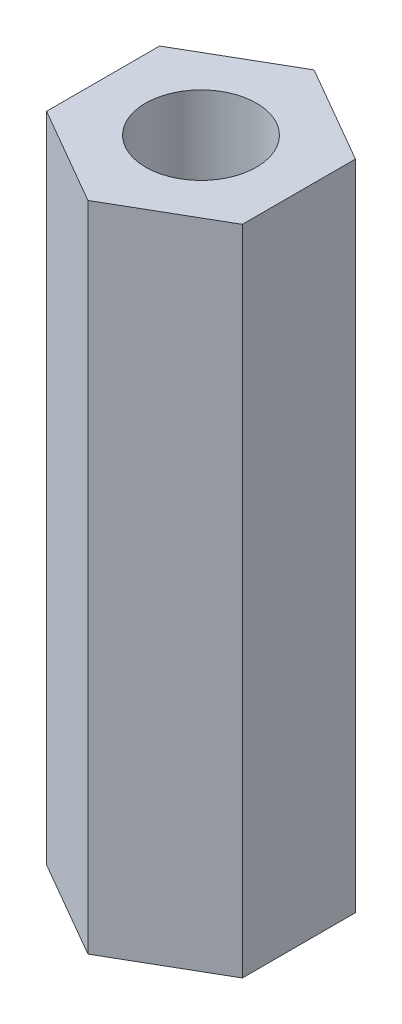
SolidWorks part; units mm, degrees
ref_plane "Front Plane" through (0, 0, 0) normal (0, 0, 1) x (1, 0, 0)
ref_plane "Top Plane" through (0, 0, 0) normal (0, 1, 0) x (1, 0, 0)
ref_plane "Right Plane" through (0, 0, 0) normal (1, 0, 0) x (0, 0, -1)
sketch "Sketch1" plane through (0, 0, 0) normal (0, 1, 0) x (1, 0, 0)
  line L1 (0, -1.7321) -> (1.5, -0.866)
  line L2 (1.5, -0.866) -> (1.5, 0.866)
  line L3 (1.5, 0.866) -> (0, 1.7321)
  line L4 (0, 1.7321) -> (-1.5, 0.866)
  line L5 (-1.5, 0.866) -> (-1.5, -0.866)
  line L6 (-1.5, -0.866) -> (0, -1.7321)
  circle A0 centre (0, 0) radius 1.5 construction
  circle A1 centre (0, 0) radius 0.85
  dimension "D2" = 1.7
  dimension "D1" = 3
extrude "Boss-Extrude1" add sketch "Sketch1" along normal blind 10
